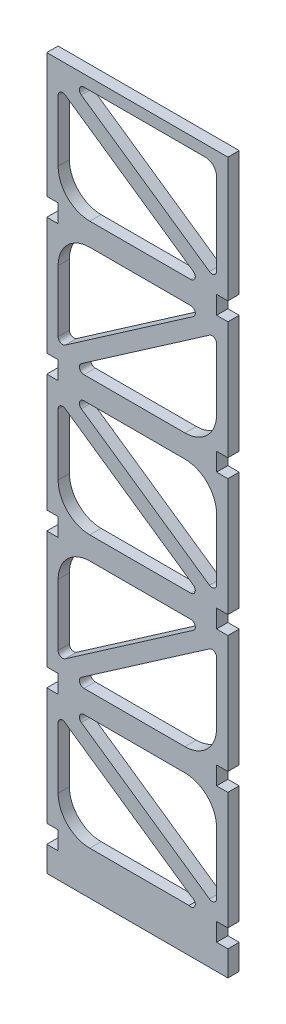
SolidWorks part; units mm, degrees
material "Balsa"
ref_plane "Front Plane" through (0, 0, 0) normal (0, 0, 1) x (1, 0, 0)
ref_plane "Top Plane" through (0, 0, 0) normal (0, 1, 0) x (1, 0, 0)
ref_plane "Right Plane" through (0, 0, 0) normal (1, 0, 0) x (0, 0, -1)
sketch "Model" plane through (0, 0, 0) normal (0, 0, 1) x (1, 0, 0)
  line L0 (77.47, 87.63) -> (20.8312, 87.63)
  line L1 (95.25, 35.3278) -> (95.25, 69.85)
  line L2 (19.3854, 83.0016) -> (91.2642, 33.2394)
  line L3 (6.35, 146.05) -> (6.35, 111.5278)
  line L4 (80.7688, 163.83) -> (24.13, 163.83)
  line L5 (10.3358, 109.4394) -> (82.2146, 159.2016)
  line L6 (77.47, 240.03) -> (20.8312, 240.03)
  line L7 (95.25, 187.7278) -> (95.25, 222.25)
  line L8 (19.3854, 235.4016) -> (91.2642, 185.6394)
  line L9 (24.13, 176.53) -> (80.7688, 176.53)
  line L10 (6.35, 228.8322) -> (6.35, 194.31)
  line L11 (82.2146, 181.1584) -> (10.3358, 230.9206)
  line L12 (91.2642, 154.7206) -> (19.3854, 104.9584)
  line L13 (95.25, 118.11) -> (95.25, 152.6322)
  line L14 (20.8312, 100.33) -> (77.47, 100.33)
  line L15 (6.35, 298.45) -> (6.35, 263.9278)
  line L16 (80.7688, 316.23) -> (24.13, 316.23)
  line L17 (10.3358, 261.8394) -> (82.2146, 311.6016)
  line L18 (88.9, 392.43) -> (20.8312, 392.43)
  line L19 (95.25, 340.1278) -> (95.25, 386.08)
  line L20 (19.3854, 387.8016) -> (91.2642, 338.0394)
  line L21 (24.13, 328.93) -> (80.7688, 328.93)
  line L22 (6.35, 381.2322) -> (6.35, 346.71)
  line L23 (82.2146, 333.5584) -> (10.3358, 383.3206)
  line L24 (24.13, 24.3357) -> (79.7674, 24.3357)
  line L25 (6.35, 76.4322) -> (6.35, 42.1157)
  line L26 (81.3163, 29.1503) -> (9.4375, 78.9125)
  line L27 (91.2642, 307.1206) -> (19.3854, 257.3584)
  line L28 (95.25, 270.51) -> (95.25, 305.0322)
  line L29 (20.8312, 252.73) -> (77.47, 252.73)
  line L30 (0, 398.78) -> (0, 0)
  line L31 (0, 0) -> (101.6, 0)
  line L32 (101.6, 398.78) -> (101.6, 0)
  line L33 (0, 398.78) -> (101.6, 398.78)
  arc A1 (91.2642, 33.2394) -> (95.25, 35.3278) centre (92.71, 35.3278) ccw
  arc A2 (20.8312, 87.63) -> (19.3854, 83.0016) centre (20.8312, 85.09) ccw
  arc A4 (82.2146, 159.2016) -> (80.7688, 163.83) centre (80.7688, 161.29) ccw
  arc A5 (6.35, 111.5278) -> (10.3358, 109.4394) centre (8.89, 111.5278) ccw
  arc A7 (91.2642, 185.6394) -> (95.25, 187.7278) centre (92.71, 187.7278) ccw
  arc A8 (20.8312, 240.03) -> (19.3854, 235.4016) centre (20.8312, 237.49) ccw
  arc A10 (10.3358, 230.9206) -> (6.35, 228.8322) centre (8.89, 228.8322) ccw
  arc A11 (80.7688, 176.53) -> (82.2146, 181.1584) centre (80.7688, 179.07) ccw
  arc A12 (95.25, 152.6322) -> (91.2642, 154.7206) centre (92.71, 152.6322) ccw
  arc A14 (19.3854, 104.9584) -> (20.8312, 100.33) centre (20.8312, 102.87) ccw
  arc A16 (82.2146, 311.6016) -> (80.7688, 316.23) centre (80.7688, 313.69) ccw
  arc A17 (6.35, 263.9278) -> (10.3358, 261.8394) centre (8.89, 263.9278) ccw
  arc A18 (95.25, 386.08) -> (88.9, 392.43) centre (88.9, 386.08) ccw
  arc A19 (91.2642, 338.0394) -> (95.25, 340.1278) centre (92.71, 340.1278) ccw
  arc A20 (20.8312, 392.43) -> (19.3854, 387.8016) centre (20.8312, 389.89) ccw
  arc A22 (10.3358, 383.3206) -> (6.35, 381.2322) centre (8.89, 381.2322) ccw
  arc A23 (80.7688, 328.93) -> (82.2146, 333.5584) centre (80.7688, 331.47) ccw
  arc A25 (9.4375, 78.9125) -> (6.35, 76.4322) centre (8.89, 76.4322) ccw
  arc A26 (79.7674, 24.3357) -> (81.3163, 29.1503) centre (80.7688, 26.67) ccw
  arc A27 (95.25, 305.0322) -> (91.2642, 307.1206) centre (92.71, 305.0322) ccw
  arc A29 (19.3854, 257.3584) -> (20.8312, 252.73) centre (20.8312, 255.27) ccw
  arc A30 (6.35, 42.1157) -> (24.13, 24.3357) centre (24.13, 42.1157) ccw
  arc A31 (6.35, 346.71) -> (24.13, 328.93) centre (24.13, 346.71) ccw
  arc A32 (6.35, 298.45) -> (24.13, 316.23) centre (24.13, 298.45) cw
  arc A33 (95.25, 270.51) -> (77.47, 252.73) centre (77.47, 270.51) cw
  arc A34 (77.47, 240.03) -> (95.25, 222.25) centre (77.47, 222.25) cw
  arc A35 (6.35, 194.31) -> (24.13, 176.53) centre (24.13, 194.31) ccw
  arc A36 (6.35, 146.05) -> (24.13, 163.83) centre (24.13, 146.05) cw
  arc A37 (77.47, 100.33) -> (95.25, 118.11) centre (77.47, 118.11) ccw
  arc A38 (77.47, 87.63) -> (95.25, 69.85) centre (77.47, 69.85) cw
  point P0 (79.7674, 26.67)
  point P72 (6.35, 24.13)
  point P74 (0, 0)
  point P94 (0, 0)
  point P95 (0, 0)
  point P97 (215.3022, 383.3206)
  point P98 (6.876, 24.13)
  dimension "D3" = 6.35
  dimension "D4" = 2.54
  dimension "D5" = 2.54
  dimension "D6" = 2.54
  dimension "D7" = 2.54
  dimension "D8" = 2.54
  dimension "D9" = 2.54
  dimension "D10" = 2.54
  dimension "D11" = 2.54
  dimension "D12" = 2.54
  dimension "D13" = 2.54
  dimension "D14" = 2.54
  dimension "D15" = 2.54
  dimension "D16" = 2.54
  dimension "D17" = 2.54
  dimension "D18" = 2.54
  dimension "D19" = 2.54
  dimension "D20" = 2.54
  dimension "D21" = 2.54
  dimension "D22" = 2.54
  dimension "D26" = 17.78
  dimension "D27" = 17.78
  dimension "D1" = 398.78
  dimension "D2" = 101.6
  dimension "D23" = 26.67
  dimension "D24" = 20.8312
  dimension "D25" = 87.4233
extrude "Boss-Extrude1" add sketch "Model" along normal blind 6.35
sketch "Sketch1" plane through (0, 0, 6.35) normal (0, 0, 1) x (1, 0, 0)
  line L0 (101.6, 0) -> (101.6, 398.78) construction
  line L1 (101.6, 328.93) -> (95.25, 328.93)
  line L2 (101.6, 328.93) -> (101.6, 318.77)
  line L3 (101.6, 318.77) -> (95.25, 318.77)
  line L4 (95.25, 328.93) -> (95.25, 318.77)
  line L5 (0, 398.78) -> (0, 0) construction
  line L6 (0, 252.73) -> (6.35, 252.73)
  line L7 (0, 252.73) -> (0, 242.57)
  line L8 (0, 242.57) -> (6.35, 242.57)
  line L9 (6.35, 252.73) -> (6.35, 242.57)
  line L10 (24.13, 328.93) -> (80.7688, 328.93) construction
  line L11 (101.6, 176.53) -> (95.25, 176.53)
  line L12 (101.6, 176.53) -> (101.6, 166.37)
  line L13 (101.6, 166.37) -> (95.25, 166.37)
  line L14 (95.25, 176.53) -> (95.25, 166.37)
  line L15 (0, 100.33) -> (6.35, 100.33)
  line L16 (0, 100.33) -> (0, 90.17)
  line L17 (0, 90.17) -> (6.35, 90.17)
  line L18 (6.35, 100.33) -> (6.35, 90.17)
  line L19 (20.8312, 252.73) -> (77.47, 252.73) construction
  line L21 (20.8312, 100.33) -> (77.47, 100.33) construction
  line L22 (24.13, 24.3357) -> (79.7674, 24.3357) construction
  line L23 (0, 328.93) -> (6.35, 328.93)
  line L24 (0, 328.93) -> (0, 318.77)
  line L25 (0, 318.77) -> (6.35, 318.77)
  line L26 (6.35, 328.93) -> (6.35, 318.77)
  line L27 (101.6, 252.73) -> (95.25, 252.73)
  line L28 (101.6, 252.73) -> (101.6, 242.57)
  line L29 (101.6, 242.57) -> (95.25, 242.57)
  line L30 (95.25, 252.73) -> (95.25, 242.57)
  line L31 (0, 176.53) -> (6.35, 176.53)
  line L32 (0, 176.53) -> (0, 166.37)
  line L33 (0, 166.37) -> (6.35, 166.37)
  line L34 (6.35, 176.53) -> (6.35, 166.37)
  line L35 (101.6, 100.33) -> (95.25, 100.33)
  line L36 (101.6, 100.33) -> (101.6, 90.17)
  line L37 (101.6, 90.17) -> (95.25, 90.17)
  line L38 (95.25, 100.33) -> (95.25, 90.17)
  line L39 (0, 24.3357) -> (6.35, 24.3357)
  line L40 (0, 24.3357) -> (0, 14.1757)
  line L41 (0, 14.1757) -> (6.35, 14.1757)
  line L42 (6.35, 24.3357) -> (6.35, 14.1757)
  line L43 (101.6, 24.3357) -> (95.25, 24.3357)
  line L44 (101.6, 24.3357) -> (101.6, 14.1757)
  line L45 (101.6, 14.1757) -> (95.25, 14.1757)
  line L46 (95.25, 24.3357) -> (95.25, 14.1757)
  line L47 (24.13, 176.53) -> (80.7688, 176.53) construction
  point P54 (0, 0)
  dimension "D1" = 6.35
  dimension "D2" = 10.16
  dimension "D3" = 10.16
  dimension "D4" = 6.35
  dimension "D5" = 6.35
  dimension "D6" = 10.16
  dimension "D7" = 6.35
  dimension "D8" = 10.16
  dimension "D9" = 10.16
  dimension "D10" = 10.16
extrude "Cut-Extrude1" cut sketch "Sketch1" against normal up to surface (6.35 mm away) contours L1 L4 L3 L2 | L27 L30 L29 L28 | L9 L6 L7 L8 | L42 L39 L40 L41 | L11 L14 L13 L12 | L26 L25 L24 L23 | L43 L46 L45 L44 | L38 L37 L36 L35 | L15 L18 L17 L16 | L31 L34 L33 L32 region at (98.425, 323.85, 6.35) region at (3.175, 247.65, 6.35) region at (98.425, 171.45, 6.35) region at (98.425, 247.65, 6.35) region at (3.175, 19.2557, 6.35) up to face at (50.8, 199.39, 0)
equation "\"thick\"=0.25"
equation "\"D1@Boss-Extrude1\"=\"thick\""
